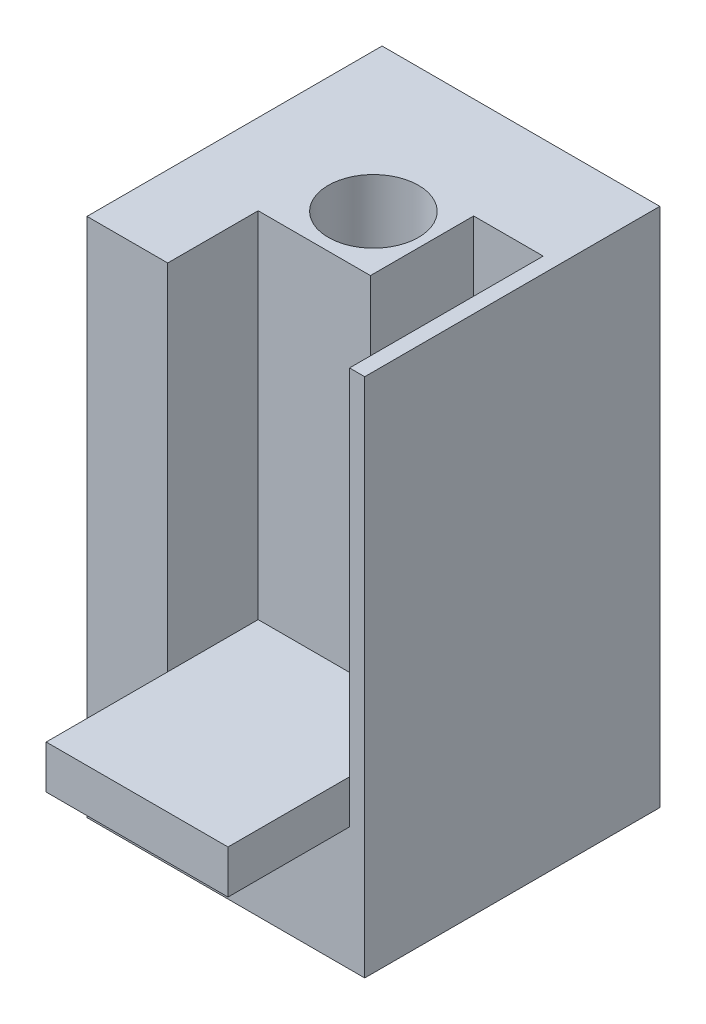
SolidWorks part; units mm, degrees
ref_plane "Front Plane" through (0, 0, 0) normal (0, 0, 1) x (1, 0, 0)
ref_plane "Top Plane" through (0, 0, 0) normal (0, 1, 0) x (1, 0, 0)
ref_plane "Right Plane" through (0, 0, 0) normal (1, 0, 0) x (0, 0, -1)
sketch "Sketch1" plane through (0, 0, 0) normal (0, 1, 0) x (1, 0, 0)
  line L1 (-10.16, 10.795) -> (10.16, 10.795)
  line L2 (-10.16, 10.795) -> (-10.16, -10.795)
  line L3 (-10.16, -10.795) -> (10.16, -10.795)
  line L4 (10.16, 10.795) -> (10.16, -10.795)
  line L5 (-10.16, 10.795) -> (10.16, -10.795) construction
  line L6 (-10.16, -10.795) -> (10.16, 10.795) construction
  circle A0 centre (0, 0) radius 8.001
  dimension "D1" = 16.002
  dimension "D2" = 21.59
  dimension "D3" = 20.32
extrude "Boss-Extrude1" add sketch "Sketch1" along normal blind 38.1
ref_plane "Plane1" through (0, 11.684, 0) normal (0, -1, 0) x (-1, 0, 0)
sketch "Sketch2" plane through (0, 11.684, 0) normal (0, -1, 0) x (-1, 0, 0)
  circle A0 centre (0, 0) radius 3.302
  circle A1 centre (0, 0) radius 8.001 construction
  circle A2 centre (0, 0) radius 8.001
  dimension "D1" = 6.604
extrude "Boss-Extrude2" add sketch "Sketch2" against normal up to surface (26.416 mm away) up to face at (0, 38.1, 0)
sketch "Sketch3" plane through (0, 38.1, 0) normal (0, 1, 0) x (1, 0, 0)
  line L0 (-4.254, -10.795) -> (-4.254, -4.177)
  line L1 (-10.16, -10.795) -> (10.16, -10.795) construction
  line L2 (-4.254, -4.177) -> (3.96, -4.177)
  line L4 (-4, -18.796) -> (-4, -5.066) construction
  line L6 (0.635, -4.431) -> (3.365, -4.431) construction
  line L7 (-4.254, -10.795) -> (4.254, -10.795)
  line L8 (3.96, -4.177) -> (3.96, 3.377)
  line L9 (3.96, 3.377) -> (9.048, 3.377)
  line L10 (9.048, 3.377) -> (9.048, -10.795)
  line L11 (9.048, -10.795) -> (4.254, -10.795)
  line L12 (4.214, 1.723) -> (4.214, -20.357) construction
  line L13 (5.614, 3.123) -> (7.954, 3.123) construction
  line L14 (8.794, -20.917) -> (8.794, 2.283) construction
  dimension "D1" = 0.254
  dimension "D2" = 0.254
  dimension "D3" = 0.254
  dimension "D4" = 0.254
  dimension "D5" = 0.254
extrude "Cut-Extrude1" cut sketch "Sketch3" against normal offset from surface (25.908 mm away) 0.254 offset beyond the face yes
sketch "Sketch4" plane through (0, 12.192, 0) normal (0, 1, 0) x (1, 0, 0)
  line L0 (-4.254, -10.795) -> (-4.254, -19.685)
  line L1 (-4.254, -19.685) -> (-4.1989, -19.685)
  line L2 (-4.1989, -19.685) -> (9.048, -19.685)
  line L3 (9.048, -19.685) -> (9.048, -10.795)
  line L4 (9.048, -10.795) -> (10.16, -10.795) construction
  line L5 (-4.254, -10.795) -> (9.048, -10.795)
  line L6 (-3.365, -19.431) -> (-0.635, -19.431) construction
  point P5 (9.048, -10.795)
  point P12 (-4.1989, -19.685)
  dimension "D1" = 0.254
extrude "Boss-Extrude3" add sketch "Sketch4" against normal blind 3.175
